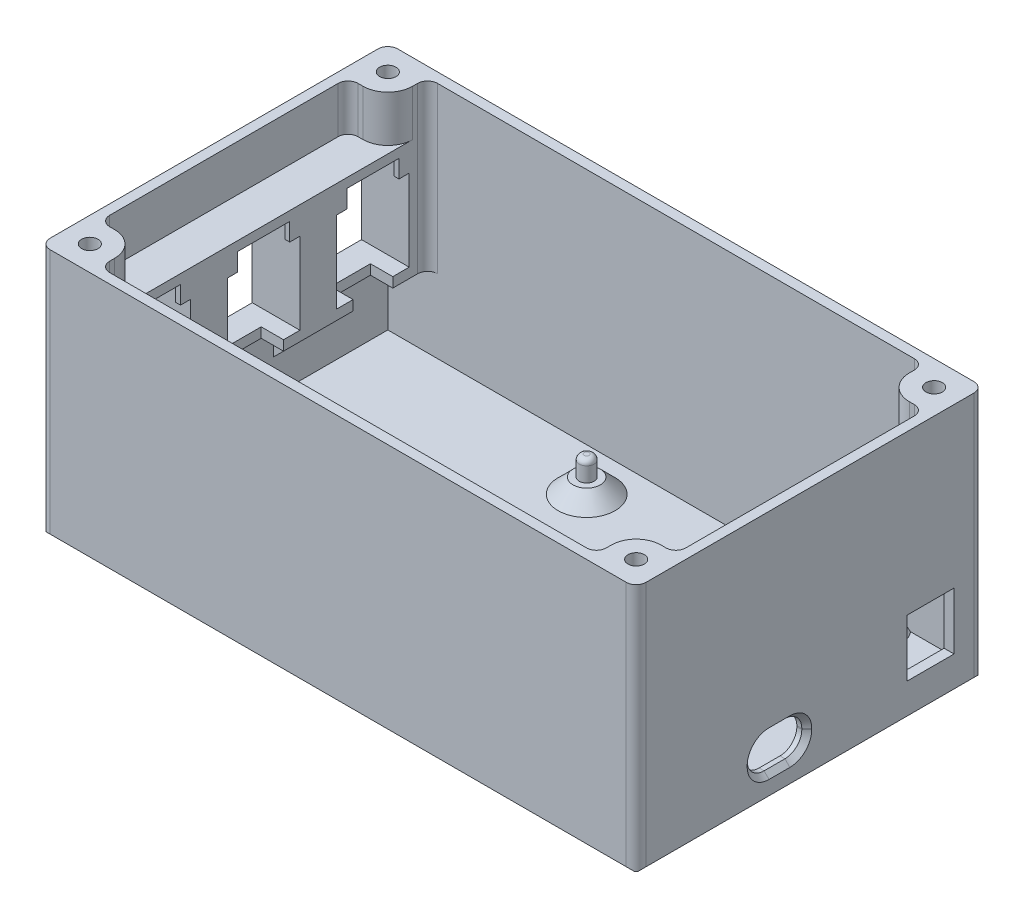
SolidWorks part; units mm, degrees
note: The reader was unsure of these and kept them because the rebuilt part matched: shared geometry of "Sketch5<2><2>".
ref_plane "Front Plane" through (0, 0, 0) normal (0, 0, 1) x (1, 0, 0)
ref_plane "Top Plane" through (0, 0, 0) normal (0, 1, 0) x (1, 0, 0)
ref_plane "Right Plane" through (0, 0, 0) normal (1, 0, 0) x (0, 0, -1)
sketch "Sketch1" plane through (0, 0, 0) normal (0, 1, 0) x (1, 0, 0)
  line L1 (-60, -35) -> (60, -35)
  line L2 (-60, -35) -> (-60, 35)
  line L3 (-60, 35) -> (60, 35)
  line L4 (60, -35) -> (60, 35)
  line L5 (-60, -35) -> (60, 35) construction
  line L6 (-60, 35) -> (60, -35) construction
  point P0 (0, 0)
  dimension "D1" = 120
  dimension "D2" = 70
extrude "Boss-Extrude1" add sketch "Sketch1" along normal blind 50
shell "Shell1" thickness 2
sketch "Sketch16" plane through (60, 0, 0) normal (1, 0, 0) x (0, 0, -1)
  line L0 (35, 50) -> (35, 0) construction
  line L1 (19.5, 18) -> (29, 18)
  line L2 (19.5, 18) -> (19.5, 6.5)
  line L3 (19.5, 6.5) -> (29, 6.5)
  line L4 (29, 18) -> (29, 6.5)
  line L5 (-35, 0) -> (35, 0) construction
  line L59 (-8.25, 11.25) -> (-4.05, 11.25)
  line L60 (-11.65, 7.85) -> (-11.65, 7.65)
  line L61 (-8.25, 4.25) -> (-4.05, 4.25)
  line L62 (-0.65, 7.85) -> (-0.65, 7.65)
  line L63 (-11.65, 11.25) -> (-0.65, 4.25) construction
  line L64 (-11.65, 4.25) -> (-0.65, 11.25) construction
  arc A4 (-4.05, 11.25) -> (-0.65, 7.85) centre (-4.05, 7.85) cw
  arc A5 (-0.65, 7.65) -> (-4.05, 4.25) centre (-4.05, 7.65) cw
  arc A6 (-11.65, 7.65) -> (-8.25, 4.25) centre (-8.25, 7.65) ccw
  arc A7 (-11.65, 7.85) -> (-8.25, 11.25) centre (-8.25, 7.85) cw
  point P38 (-6.15, 7.75)
  point P44 (24.25, 18)
  point P45 (19.5, 12.25)
  dimension "D9" = 3.4
  dimension "D1" = 6
  dimension "D2" = 9.5
  dimension "D3" = 11.5
  dimension "D4" = 6.5
  dimension "D5" = 30.4
  dimension "D6" = 4.5
  dimension "D7" = 11
  dimension "D8" = 7
extrude "Cut-Extrude9" cut sketch "Sketch16" against normal up to surface (2 mm away) up to face at (58, 26, 0)
chamfer "Chamfer2" distance 1 angle 45 8 edges at (60, 4.25, 6.15) (60, 5.2458, 1.6458) (60, 5.2458, 10.6542) (60, 7.75, 0.65) (60, 7.75, 11.65) (60, 10.2542, 1.6458) (60, 10.2542, 10.6542) (60, 11.25, 6.15)
chamfer "Chamfer3" distance 0.4 angle 45 4 edges at (60, 0, 0) (0, 0, -35) (-60, 0, 0) (0, 0, 35)
sketch "Sketch17" plane through (0, 2, 0) normal (0, 1, 0) x (1, 0, 0)
  line L0 (58, 33) -> (-58, 33) construction
  line L1 (58, -33) -> (58, 33) construction
  circle A0 centre (-9.3433, 24.38) radius 2.75
  circle A1 centre (42.7267, 29.46) radius 2.75
  circle A2 centre (41.4567, -18.8) radius 2.75
  circle A3 centre (-9.3433, -3.56) radius 2.75
  dimension "D1" = 5.5
  dimension "D2" = 5.08
  dimension "D3" = 33.02
  dimension "D4" = 48.26
  dimension "D5" = 1.27
  dimension "D6" = 52.07
  dimension "D7" = 52.07
  dimension "D8" = 3.54
  dimension "D9" = 15.2733
extrude "Boss-Extrude7" add sketch "Sketch17" along normal blind 3
sketch "Sketch18" plane through (0, 5, 0) normal (0, 1, 0) x (1, 0, 0)
  circle A0 centre (-9.3433, 24.38) radius 1.5
  circle A1 centre (-9.3433, -3.56) radius 1.5
  circle A2 centre (41.4567, -18.8) radius 1.5
  circle A3 centre (42.7267, 29.46) radius 1.5
  dimension "D1" = 3
extrude "Boss-Extrude8" add sketch "Sketch18" along normal blind 4
chamfer "Chamfer4" distance 3 angle 45 4 edges at (41.4567, 2, 16.05) (-9.3433, 2, 0.81) (42.7267, 2, -32.21) (-9.3433, 2, -27.13)
fillet "Fillet1" radius 1 4 edges at (-9.3433, 9, 5.06) (41.4567, 9, 20.3) (42.7267, 9, -27.96) (-9.3433, 9, -22.88)
sketch "Sketch5<2>" plane through (-58, 2.1348, 2.5464) normal (1, 0, 0) x (0, 0, -1)
  line L0 (-30.4536, -0.1348) -> (-30.4536, 47.8652) construction
  line L1 (-26.7536, 33.0652) -> (-12.1536, 33.0652)
  line L2 (-26.7536, 33.0652) -> (-26.7536, 16.6652)
  line L3 (-26.7536, 16.6652) -> (-12.1536, 16.6652)
  line L4 (-12.1536, 33.0652) -> (-12.1536, 16.6652)
  line L5 (-30.4536, 47.8652) -> (35.5464, 47.8652) construction
  point P4 (-19.4536, 16.6652)
  point P7 (-26.7536, 24.8652)
  dimension "D1" = 14.6
  dimension "D2" = 16.4
  dimension "D3" = 11
  dimension "D4" = 23
extrude "Cut-Extrude1" cut sketch "Sketch5<2>" against normal up to next and the other way blind 10
sketch "Sketch6" plane through (-58, 11, -1) normal (1, 0, 0) x (0, 0, -1)
  line L0 (-15.7, 24.2) -> (-30.3, 24.2) construction
  line L1 (-32.3, 5.8) -> (-13.7, 5.8)
  line L2 (-32.3, 5.8) -> (-32.3, 29.7)
  line L3 (-32.3, 29.7) -> (-13.7, 29.7)
  line L4 (-13.7, 5.8) -> (-13.7, 29.7)
  line L5 (-30.3, 7.8) -> (-15.7, 7.8) construction
  line L6 (-30.3, 24.2) -> (-30.3, 7.8) construction
  line L7 (-15.7, 7.8) -> (-15.7, 24.2) construction
  dimension "D1" = 5.5
  dimension "D2" = 2
  dimension "D3" = 2
  dimension "D4" = 2
extrude "Boss-Extrude5" add sketch "Sketch6" along normal offset from surface (8 mm away) 10 up to face at (-60, 25.2, 0)
extrude "Cut-Extrude2" cut sketch "Sketch5<2><2>" along normal up to next
sketch "Sketch5<2><2>" plane through (-58, 2.1348, 2.5464) normal (1, 0, 0) x (0, 0, -1) same geometry as "Sketch5<2>"
sketch "Sketch12" plane through (-50, 6.5674, 0.7732) normal (1, 0, 0) x (0, 0, -1)
  line L1 (-28.5268, 28.6326) -> (-13.9268, 28.6326)
  line L2 (-28.5268, 28.6326) -> (-28.5268, 33.1326)
  line L3 (-28.5268, 33.1326) -> (-13.9268, 33.1326)
  line L4 (-13.9268, 28.6326) -> (-13.9268, 33.1326)
  dimension "D1" = 4.5
extrude "Cut-Extrude7" cut sketch "Sketch12" against normal offset from surface (4.5 mm away) 5.5
sketch "Sketch13" plane through (-50, 6.5674, 0.7732) normal (1, 0, 0) x (0, 0, -1)
  line L1 (-28.5268, 33.1326) -> (-13.9268, 33.1326)
  line L2 (-28.5268, 33.1326) -> (-28.5268, 28.6326)
  line L3 (-28.5268, 28.6326) -> (-13.9268, 28.6326)
  line L4 (-13.9268, 33.1326) -> (-13.9268, 28.6326)
  line L5 (-26.4768, 32.2326) -> (-15.9768, 32.2326)
  line L6 (-26.4768, 32.2326) -> (-26.4768, 28.6326)
  line L7 (-26.4768, 28.6326) -> (-15.9768, 28.6326)
  line L8 (-15.9768, 32.2326) -> (-15.9768, 28.6326)
  point P10 (-21.2268, 32.2326)
  point P11 (-21.2268, 33.1326)
  dimension "D1" = 10.5
  dimension "D2" = 3.6
extrude "Boss-Extrude6" add sketch "Sketch13" against normal offset from surface (1 mm away) 9
chamfer "Chamfer1" distance 0.4 angle 45 4 edges at (-60, 18.8, 22) (-60, 27, 29.3) (-60, 35.2, 22) (-60, 27, 14.7)
sketch "Sketch14" plane through (-50, 6.5674, 0.7732) normal (1, 0, 0) x (0, 0, -1)
  line L0 (-28.5268, 12.2326) -> (-13.9268, 12.2326) construction
  line L1 (-25.2268, 12.2326) -> (-17.2268, 12.2326)
  line L2 (-25.2268, 12.2326) -> (-25.2268, 10.2326)
  line L3 (-25.2268, 10.2326) -> (-17.2268, 10.2326)
  line L4 (-17.2268, 12.2326) -> (-17.2268, 10.2326)
  line L5 (-30.5268, 10.2326) -> (-11.9268, 10.2326) construction
  line L6 (-26.4768, 32.2326) -> (-15.9768, 32.2326) construction
  point P10 (-21.2268, 32.2326)
  point P11 (-21.2268, 12.2326)
  dimension "D1" = 8
extrude "Cut-Extrude8" cut sketch "Sketch14" against normal offset from surface (4.5 mm away) 5.5
other "RJ-45_mantel<1>"
pattern_linear "LPattern3" count 3 spacing 22 along (0, 0, -1) of "Cut-Extrude1", "Boss-Extrude5", "Cut-Extrude2", "Cut-Extrude7", "Boss-Extrude6", "Chamfer1", "Cut-Extrude8"
sketch "Sketch19" plane through (-60, 0, 0) normal (-1, 0, 0) x (0, 0, 1)
  line L1 (-33, 15.4) -> (33, 15.4)
  line L2 (-33, 15.4) -> (-33, 3.4)
  line L3 (-33, 3.4) -> (33, 3.4)
  line L4 (33, 15.4) -> (33, 3.4)
  line L9 (-35, 50) -> (35, 50) construction
  line L10 (0, 18.4) -> (0, 0.4) construction
  line L11 (7.7, 18.4) -> (-7.7, 18.4) construction
  line L12 (-35, 0.4) -> (35, 0.4) construction
  point P6 (0, 50)
  point P7 (0, 15.4)
  point P14 (-33, 9.4)
  point P15 (0, 9.4)
  dimension "D1" = 12
  dimension "D2" = 66
extrude "Cut-Extrude10" cut sketch "Sketch19" against normal blind 0.4
sketch "Sketch20" plane through (0, 50, 0) normal (0, 1, 0) x (1, 0, 0)
  line L0 (60, 35) -> (-60, 35) construction
  line L1 (58, 33) -> (50, 33)
  line L2 (58, 33) -> (58, 25)
  line L3 (58, 25) -> (55, 25)
  line L4 (50, 33) -> (50, 30)
  line L5 (60, -35) -> (60, 35) construction
  circle A0 centre (55, 30) radius 1.65
  arc A1 (55, 25) -> (50, 30) centre (55, 30) cw
  dimension "D5" = 3.3
  dimension "D6" = 5
  dimension "D1" = 10
  dimension "D2" = 10
  dimension "D3" = 5
  dimension "D4" = 5
extrude "Boss-Extrude9" add sketch "Sketch20" against normal up to surface (9.3 mm away) up to face at (-54, 40.7, -22)
mirror "Mirror1" about plane through (0, 0, 0) normal (0, 0, 1) of "Boss-Extrude9" second plane through (0, 0, 0) second plane normal (1, 0, 0)
sketch "Sketch21" plane through (0, 0, 12.7) normal (0, 0, -1) x (-1, 0, 0)
  line L1 (58, 40.7) -> (50, 40.7)
  line L2 (58, 40.7) -> (58, 16.8)
  line L3 (58, 16.8) -> (50, 16.8)
  line L4 (50, 40.7) -> (50, 16.8)
extrude "Boss-Extrude10" add sketch "Sketch21" along normal up to surface (3.4 mm away) up to face at (-54, 28.75, 9.3)
sketch "Sketch22" plane through (0, 0, -9.3) normal (0, 0, -1) x (-1, 0, 0)
  line L1 (58, 40.7) -> (50, 40.7)
  line L2 (58, 40.7) -> (58, 16.8)
  line L3 (58, 16.8) -> (50, 16.8)
  line L4 (50, 40.7) -> (50, 16.8)
extrude "Boss-Extrude11" add sketch "Sketch22" along normal up to surface (3.4 mm away) up to face at (-54, 28.75, -12.7)
sketch "Sketch23" plane through (0, 0, 31.3) normal (0, 0, 1) x (1, 0, 0)
  line L1 (-58, 40.7) -> (-50, 40.7)
  line L2 (-58, 40.7) -> (-58, 16.8)
  line L3 (-58, 16.8) -> (-50, 16.8)
  line L4 (-50, 40.7) -> (-50, 16.8)
extrude "Boss-Extrude12" add sketch "Sketch23" along normal up to next
sketch "Sketch24" plane through (0, 0, -31.3) normal (0, 0, -1) x (-1, 0, 0)
  line L1 (58, 40.7) -> (50, 40.7)
  line L2 (58, 40.7) -> (58, 16.8)
  line L3 (58, 16.8) -> (50, 16.8)
  line L4 (50, 40.7) -> (50, 16.8)
extrude "Boss-Extrude13" add sketch "Sketch24" along normal up to next
ref_plane "Plane1" through (0, 0, 11) normal (0, 0, 1) x (1, 0, 0)
sketch "Sketch25" plane through (0, 0, 11) normal (0, 0, 1) x (1, 0, 0)
  line L0 (-50, 16.8) -> (-58, 8.8)
  line L1 (-58, 16.8) -> (-58, 2) construction
  dimension "D1" = 45
rib "Rib1" sketch "Sketch25" sketch "Sketch25" thickness 2 extrusion direction parallel to sketch draft on no parameters "D1"=2
mirror "Mirror2" about plane through (0, 0, 0) normal (0, 0, 1) of "Rib1"
fillet "Fillet2" radius 2 16 edges at (-59.8, 0.2, 34.8) (-59.8, 0.2, -34.8) (59.8, 0.2, 34.8) (59.8, 0.2, -34.8) (58, 45.35, -25) (50, 45.35, -33) (-50, 33.4, -33) (-58, 45.35, -25) (50, 45.35, 33) (58, 45.35, 25) (-58, 45.35, 25) (-50, 33.4, 33) (60, 25.2, 35) (-60, 25.2, 35) (-60, 25.2, -35) (60, 25.2, -35)
equation "\"brete\"= 70"
equation "\"lengte\"= 120"
equation "\"hogte\"= 50"
equation "\"D2@Sketch1\"=\"brete\""
equation "\"D1@Sketch1\"=\"lengte\""
equation "\"D1@Boss-Extrude1\"=\"hogte\""
equation "\"wand_dikte\"= 2"
equation "\"D1@Shell1\"=\"wand_dikte\""
equation "\"D3@LPattern3\"=(\"brete\"-2*\"wand_dikte\")/3"
